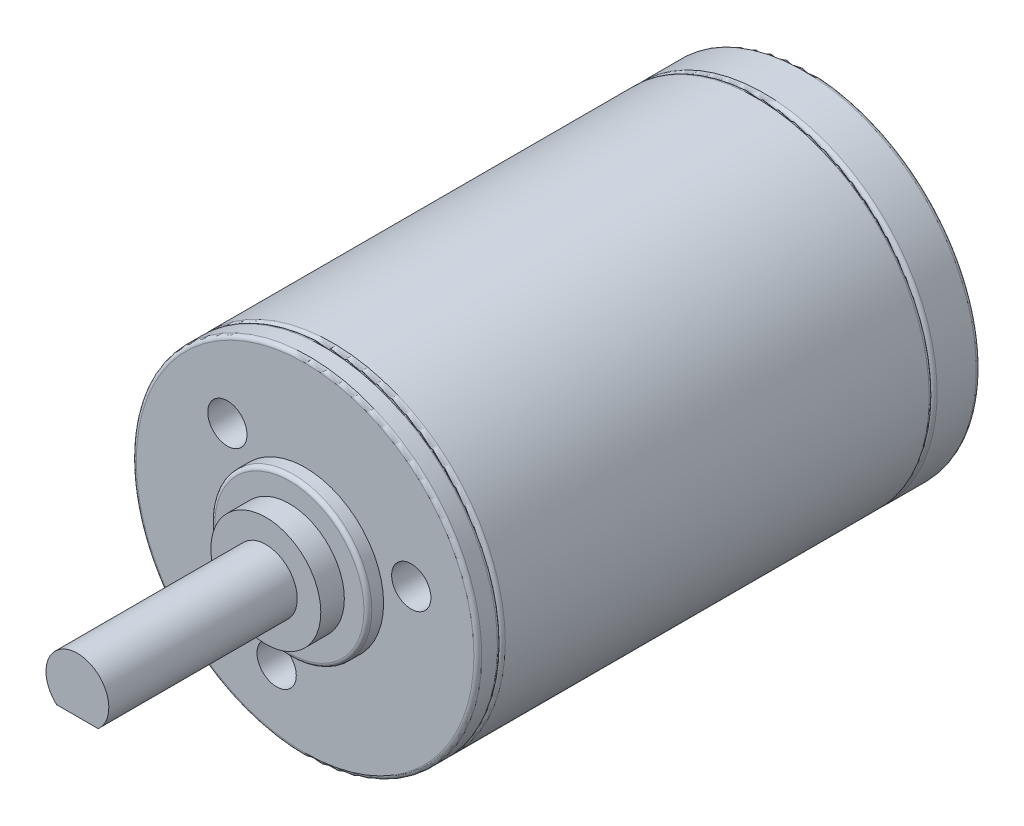
SolidWorks part; units mm, degrees
ref_plane "Plan de face" through (0, 0, 0) normal (0, 0, 1) x (1, 0, 0)
ref_plane "Plan de dessus" through (0, 0, 0) normal (0, 1, 0) x (1, 0, 0)
ref_plane "Plan de droite" through (0, 0, 0) normal (1, 0, 0) x (0, 0, -1)
sketch "Esquisse1" plane through (0, 0, 0) normal (0, 0, 1) x (1, 0, 0)
  circle A0 centre (0, 0) radius 11
  dimension "D1" = 22
extrude "Boss.-Extru.1" add sketch "Esquisse1" along normal blind 27.5
fillet "Congé1" radius 0.25 2 edges at (11, 0, 27.5) (11, 0, 0)
sketch "Esquisse4" plane through (0, 0, 0) normal (0, 0, -1) x (-1, 0, 0)
  circle A0 centre (0, 0) radius 11
extrude "Boss.-Extru.5" add sketch "Esquisse4" along normal blind 3
fillet "Congé2" radius 0.25 2 edges at (-11, 0, -3) (-11, 0, 0)
sketch "Esquisse5" plane through (0, 0, 27.5) normal (0, 0, 1) x (1, 0, 0)
  circle A0 centre (0, 0) radius 11
extrude "Boss.-Extru.6" add sketch "Esquisse5" along normal blind 1.5
fillet "Congé3" radius 0.25 2 edges at (11, 0, 27.5) (11, 0, 29)
sketch "Esquisse6" plane through (0, 0, 29) normal (0, 0, 1) x (1, 0, 0)
  circle A0 centre (0, 0) radius 5
  dimension "D1" = 10
extrude "Boss.-Extru.7" add sketch "Esquisse6" along normal blind 1
fillet "Congé4" radius 0.25 1 edges at (5, 0, 30)
sketch "Esquisse7" plane through (0, 0, 30) normal (0, 0, 1) x (1, 0, 0)
  circle A0 centre (0, 0) radius 3.5
  dimension "D1" = 7
extrude "Boss.-Extru.8" add sketch "Esquisse7" along normal blind 1.5
sketch "Esquisse8" plane through (0, 0, 31.5) normal (0, 0, 1) x (1, 0, 0)
  circle A0 centre (0, 0) radius 2
  dimension "D1" = 4
extrude "Boss.-Extru.9" add sketch "Esquisse8" along normal blind 12
sketch "Esquisse9" plane through (0, 0, 43.5) normal (0, 0, 1) x (1, 0, 0)
  line L0 (-1.3229, -1.5) -> (1.3229, -1.5)
  arc A0 (-1.3229, -1.5) -> (1.3229, -1.5) centre (0, 0) ccw
  circle A1 centre (0, 0) radius 2 construction
  dimension "D1" = 1.5
extrude "Enlèv. mat.-Extru.1" cut sketch "Esquisse9" against normal blind 8.5
sketch "Esquisse10" plane through (0, 0, 29) normal (0, 0, 1) x (1, 0, 0)
  line L0 (0, 0) -> (10.3837, 2.7823) construction
  line L1 (0, 0) -> (-7.6014, 7.6014) construction
  line L2 (0, 0) -> (-2.7823, -10.3837) construction
  line L3 (0, 16.1227) -> (0, -13.5381) construction
  circle A0 centre (0, 0) radius 10.75 construction
  circle A1 centre (6.7615, 1.8117) radius 1.25
  circle A2 centre (-1.8117, -6.7615) radius 1.25
  circle A3 centre (-4.9497, 4.9497) radius 1.25
  point P16 (0, 0)
  dimension "D1" = 2.5
  dimension "D2" = 7
  dimension "D3" = 120
  dimension "D4" = 120
  dimension "D6" = 15
  dimension "D5" = 3
extrude "Enlèv. mat.-Extru.2" cut sketch "Esquisse10" against normal blind 3
